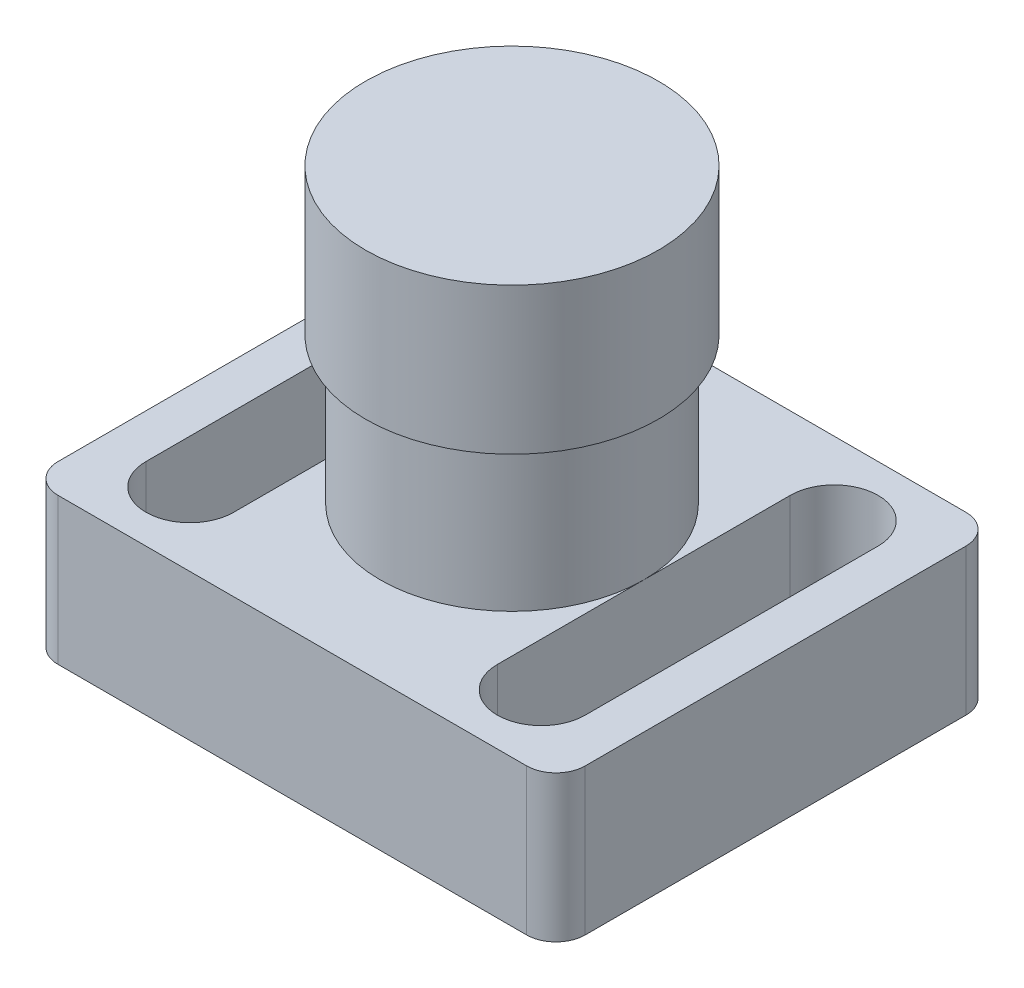
SolidWorks part; units mm, degrees
ref_plane "Front Plane" through (0, 0, 0) normal (0, 0, 1) x (1, 0, 0)
ref_plane "Top Plane" through (0, 0, 0) normal (0, 1, 0) x (1, 0, 0)
ref_plane "Right Plane" through (0, 0, 0) normal (1, 0, 0) x (0, 0, -1)
sketch "Sketch1" plane through (0, 0, 0) normal (0, 1, 0) x (1, 0, 0)
  line L0 (-8.4143, 0) -> (6, 0) construction
  line L1 (0, -5.6176) -> (0, 6.2927) construction
  line L2 (6, -5) -> (6, 5) construction
  line L3 (4.5, -5) -> (4.5, 5)
  line L4 (7.5, -5) -> (7.5, 5)
  line L5 (-6, -5) -> (-6, 5) construction
  line L6 (-4.5, -5) -> (-4.5, 5)
  line L7 (-7.5, -5) -> (-7.5, 5)
  line L9 (-8, 7.5) -> (8, 7.5)
  line L10 (-9, 6.5) -> (-9, -6.5)
  line L11 (-8, -7.5) -> (8, -7.5)
  line L12 (9, 6.5) -> (9, -6.5)
  line L13 (-9, 7.5) -> (9, -7.5) construction
  line L14 (-9, -7.5) -> (9, 7.5) construction
  circle A0 centre (0, 0) radius 4
  arc A1 (4.5, -5) -> (7.5, -5) centre (6, -5) ccw
  arc A2 (7.5, 5) -> (4.5, 5) centre (6, 5) ccw
  arc A3 (-4.5, -5) -> (-7.5, -5) centre (-6, -5) cw
  arc A4 (-7.5, 5) -> (-4.5, 5) centre (-6, 5) cw
  arc A5 (-9, -6.5) -> (-8, -7.5) centre (-8, -6.5) ccw
  arc A6 (-8, 7.5) -> (-9, 6.5) centre (-8, 6.5) ccw
  arc A7 (8, 7.5) -> (9, 6.5) centre (8, 6.5) cw
  arc A8 (8, -7.5) -> (9, -6.5) centre (8, -6.5) ccw
  circle A9 centre (0, 0) radius 4.5
  point P9 (6, 0)
  point P16 (-6, 0)
  dimension "D1" = 8
  dimension "D5" = 1
  dimension "D2" = 3
  dimension "D3" = 10
  dimension "D4" = 12
  dimension "D6" = 18
  dimension "D7" = 15
  dimension "D8" = 0.5
extrude "Boss-Extrude1" add sketch "Sketch1" along normal blind 5 contours L11 A8 L12 A7 L9 A6 L10 A5 A9 L3 A2 L4 A1 L6 A3 L7 A4 | A4 L7 A3 L6 | A9 A0 | A0 | L4 A2 L3 A1 region at (-6, 0, 0) region at (0, 0, 4.3727) region at (6, 0, 0) region at (0, 0, -7.2657) region at (0, 0, 0)
extrude "Cut-Extrude2" cut sketch "Sketch1<5>" along normal through all contours A4 L7 A3 L6 | L4 A2 L3 A1 | A0 region at (-6, 0, 0) region at (6, 0, 0) region at (0, 0, 0)
sketch "Sketch1<5>" plane through (0, 0, 0) normal (0, 1, 0) x (1, 0, 0) same geometry as "Sketch1"
extrude "Boss-Extrude4" add sketch "Sketch1<6>" along normal blind 10 contours A9 A0 region at (0, 0, 4.3727)
sketch "Sketch1<6>" plane through (0, 0, 0) normal (0, 1, 0) x (1, 0, 0) same geometry as "Sketch1"
sketch "Sketch3" plane through (0, 10, 0) normal (0, 1, 0) x (1, 0, 0)
  circle A0 centre (0, 0) radius 5
  dimension "D1" = 10
extrude "Boss-Extrude5" add sketch "Sketch3" along normal blind 5
